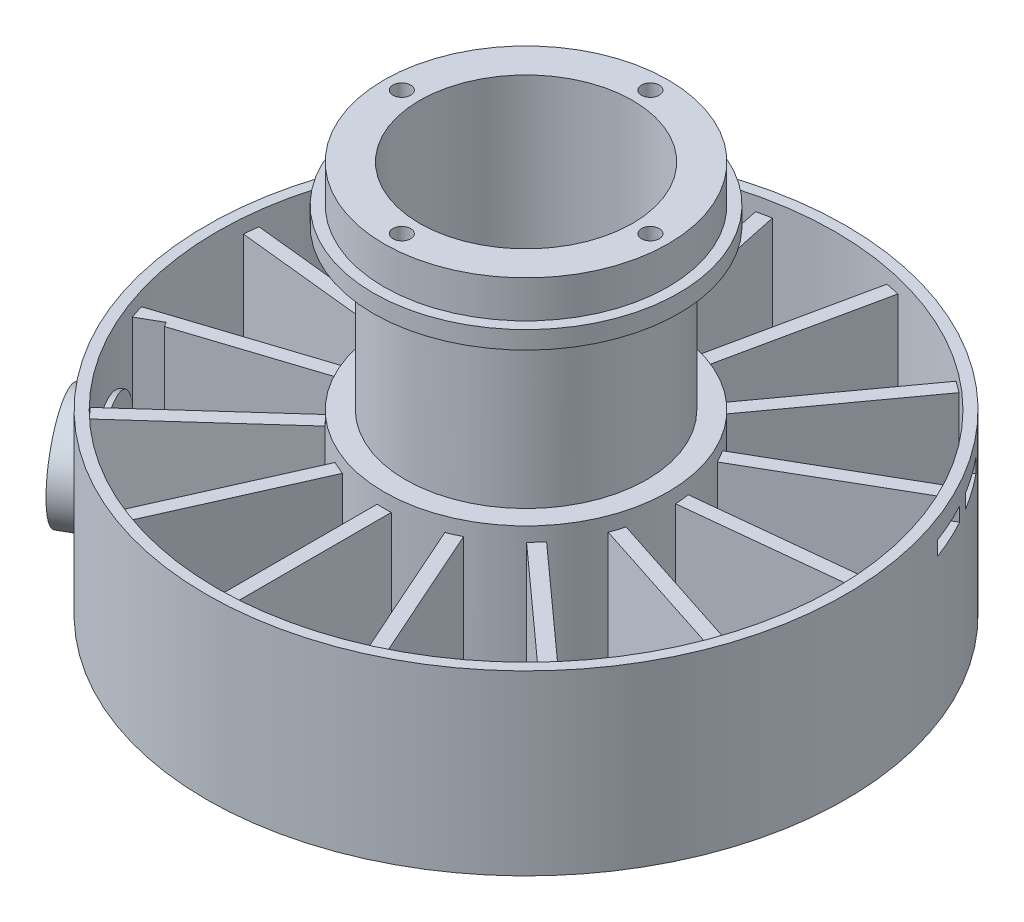
SolidWorks part; units mm, degrees
ref_plane "Front Plane" through (0, 0, 0) normal (0, 0, 1) x (1, 0, 0)
ref_plane "Top Plane" through (0, 0, 0) normal (0, 1, 0) x (1, 0, 0)
ref_plane "Right Plane" through (0, 0, 0) normal (1, 0, 0) x (0, 0, -1)
sketch "Sketch1" plane through (0, 0, 0) normal (0, 1, 0) x (1, 0, 0)
  circle A0 centre (0, 0) radius 90
  dimension "D1" = 180
extrude "Boss-Extrude1" add sketch "Sketch1" along normal blind 50
sketch "Sketch2" plane through (0, 0, 0) normal (0, -1, 0) x (1, 0, 0)
  line L0 (0, 90) -> (0, 0) construction
  line L1 (-2, 89.9778) -> (-2, 0)
  line L2 (-2, 0) -> (2, 0)
  line L3 (2, 0) -> (2, 89.9778)
  line L4 (34.7702, 83.0123) -> (-1.8271, 0.8135)
  line L5 (-1.8271, 0.8135) -> (1.8271, -0.8135)
  line L6 (1.8271, -0.8135) -> (38.4243, 81.3853)
  line L7 (36.6063, 82.2191) -> (0, 0) construction
  line L8 (65.5283, 61.6932) -> (-1.3383, 1.4863)
  line L9 (-1.3383, 1.4863) -> (1.3383, -1.4863)
  line L10 (1.3383, -1.4863) -> (68.2048, 58.7206)
  line L11 (66.883, 60.2218) -> (0, 0) construction
  line L12 (84.9559, 29.7068) -> (-0.618, 1.9021)
  line L13 (-0.618, 1.9021) -> (0.618, -1.9021)
  line L14 (0.618, -1.9021) -> (86.192, 25.9025)
  line L15 (85.5951, 27.8115) -> (0, 0) construction
  line L16 (89.6939, -7.4162) -> (0.2091, 1.989)
  line L17 (0.2091, 1.989) -> (-0.2091, -1.989)
  line L18 (-0.2091, -1.989) -> (89.2758, -11.3943)
  line L19 (89.507, -9.4076) -> (0, 0) construction
  line L20 (78.923, -43.2568) -> (1, 1.7321)
  line L21 (1, 1.7321) -> (-1, -1.7321)
  line L22 (-1, -1.7321) -> (76.923, -46.7209)
  line L23 (77.9423, -45) -> (0, 0) construction
  line L24 (54.5056, -71.618) -> (1.618, 1.1756)
  line L25 (1.618, 1.1756) -> (-1.618, -1.1756)
  line L26 (-1.618, -1.1756) -> (51.2696, -73.9691)
  line L27 (52.9007, -72.8115) -> (0, 0) construction
  line L28 (20.6637, -87.5957) -> (1.9563, 0.4158)
  line L29 (1.9563, 0.4158) -> (-1.9563, -0.4158)
  line L30 (-1.9563, -0.4158) -> (16.7511, -88.4274)
  line L31 (18.7121, -88.0333) -> (0, 0) construction
  line L32 (-16.7511, -88.4274) -> (1.9563, -0.4158)
  line L33 (1.9563, -0.4158) -> (-1.9563, 0.4158)
  line L34 (-1.9563, 0.4158) -> (-20.6637, -87.5957)
  line L35 (-18.7121, -88.0333) -> (0, 0) construction
  line L36 (-51.2696, -73.9691) -> (1.618, -1.1756)
  line L37 (1.618, -1.1756) -> (-1.618, 1.1756)
  line L38 (-1.618, 1.1756) -> (-54.5056, -71.618)
  line L39 (-52.9007, -72.8115) -> (0, 0) construction
  line L40 (-76.923, -46.7209) -> (1, -1.7321)
  line L41 (1, -1.7321) -> (-1, 1.7321)
  line L42 (-1, 1.7321) -> (-78.923, -43.2568)
  line L43 (-77.9423, -45) -> (0, 0) construction
  line L44 (-89.2758, -11.3943) -> (0.2091, -1.989)
  line L45 (0.2091, -1.989) -> (-0.2091, 1.989)
  line L46 (-0.2091, 1.989) -> (-89.6939, -7.4162)
  line L47 (-89.507, -9.4076) -> (0, 0) construction
  line L48 (-86.192, 25.9025) -> (-0.618, -1.9021)
  line L49 (-0.618, -1.9021) -> (0.618, 1.9021)
  line L50 (0.618, 1.9021) -> (-84.9559, 29.7068)
  line L51 (-85.5951, 27.8115) -> (0, 0) construction
  line L52 (-68.2048, 58.7206) -> (-1.3383, -1.4863)
  line L53 (-1.3383, -1.4863) -> (1.3383, 1.4863)
  line L54 (1.3383, 1.4863) -> (-65.5283, 61.6932)
  line L55 (-66.883, 60.2218) -> (0, 0) construction
  line L56 (-38.4243, 81.3853) -> (-1.8271, -0.8135)
  line L57 (-1.8271, -0.8135) -> (1.8271, 0.8135)
  line L58 (1.8271, 0.8135) -> (-34.7702, 83.0123)
  line L59 (-36.6063, 82.2191) -> (0, 0) construction
  circle A0 centre (0, 0) radius 90
  point P155 (0, 0)
  circle M2 centre (0, 0) radius 90
  dimension "D1" = 180
  dimension "D2" = 4
  dimension "D3" = 15
extrude "Cut-Extrude1" cut sketch "Sketch2" against normal blind 50 contours L48 L46 M2 | L52 L50 M2 | L56 L54 M2 | L58 L1 M2 | L4 L3 M2 | L8 L6 M2 | L12 L10 M2 | L16 L14 M2 | L20 L18 M2 | L24 L22 M2 | L28 L26 M2 | L32 L30 M2 | L36 L34 M2 | L40 L38 M2 | L44 L42 M2 region at (-13.0686, 0, 61.4828) region at (13.0686, 0, 61.4828) region at (-36.9461, 0, 50.8519) region at (36.9461, 0, 50.8519) region at (-54.4352, 0, 31.4282) region at (54.4352, 0, 31.4282) region at (-62.5121, 0, 6.5703) region at (62.5121, 0, 6.5703) region at (-59.78, 0, -19.4237) region at (59.78, 0, -19.4237) region at (-46.7114, 0, -42.0591) region at (46.7114, 0, -42.0591) region at (-25.566, 0, -57.4222) region at (25.566, 0, -57.4222) region at (0, 0, -62.8564)
sketch "Sketch4" plane through (0, 50, 0) normal (0, 1, 0) x (1, 0, 0)
  circle A0 centre (0, 0) radius 40
  dimension "D1" = 80
extrude "Cut-Extrude2" cut sketch "Sketch4" against normal through all
sketch "Sketch5" plane through (0, 50, 0) normal (0, 1, 0) x (1, 0, 0)
  circle A0 centre (0, 0) radius 40
  circle A1 centre (0, 0) radius 34
extrude "Boss-Extrude2" add sketch "Sketch5" against normal blind 50
sketch "Sketch9" plane through (0, 50, 0) normal (0, 1, 0) x (1, 0, 0)
  circle A0 centre (0, 0) radius 30
  circle A2 centre (0, 0) radius 34
  circle A4 centre (0, 0) radius 34 construction
  dimension "D1" = 60
extrude "Boss-Extrude3" add sketch "Sketch9" against normal blind 15 and the other way blind 50
sketch "Sketch10" plane through (0, 100, 0) normal (0, 1, 0) x (1, 0, 0)
  circle A0 centre (0, 0) radius 40
  circle A1 centre (0, 0) radius 30 construction
  circle A2 centre (0, 0) radius 30
extrude "Boss-Extrude4" add sketch "Sketch10" along normal blind 10.5
sketch "Sketch11" plane through (0, 0, 0) normal (0, -1, 0) x (1, 0, 0)
  circle A0 centre (0, 0) radius 90
  circle A1 centre (0, 0) radius 87
  dimension "D1" = 174
extrude "Boss-Extrude5" add sketch "Sketch11" against normal up to surface (50 mm away) up to face at (13.5105, 50, -63.5619)
sketch "Sketch12" plane through (0, 50, 0) normal (0, 1, 0) x (1, 0, 0)
  circle A0 centre (0, 0) radius 40
  circle A1 centre (0, 0) radius 87
extrude "Cut-Extrude3" cut sketch "Sketch12" against normal blind 4
sketch "Sketch13" plane through (0, 0, 0) normal (0, -1, 0) x (1, 0, 0)
  circle A0 centre (0, 0) radius 87
extrude "Cut-Extrude4" cut sketch "Sketch13" against normal blind 4
ref_plane "Plane1" through (0, 110.5, 0) normal (0, 1, 0) x (1, 0, 0)
sketch "Sketch15" plane through (0, 100, 0) normal (0, -1, 0) x (1, 0, 0)
  circle A0 centre (0, 0) radius 43
  circle A1 centre (0, 0) radius 34 construction
  circle A2 centre (0, 0) radius 34
  dimension "D1" = 86
extrude "Boss-Extrude6" add sketch "Sketch15" along normal blind 5
sketch "Sketch14" plane through (0, 110.5, 0) normal (0, 1, 0) x (1, 0, 0)
  circle A0 centre (0, 0) radius 35
  circle A1 centre (-35, 0) radius 2.5
  circle A2 centre (0, 35) radius 2.5
  circle A3 centre (35, 0) radius 2.5
  circle A4 centre (0, -35) radius 2.5
  arc A5 (76.3243, 41.7565) -> (74.3243, 45.2206) centre (0, 0) ccw construction
  arc A6 (76.3243, 41.7565) -> (74.3243, 45.2206) centre (0, 0) ccw
  point P3 (-35, 0)
  point P4 (0, 35)
  point P5 (35, 0)
  point P6 (0, -35)
  point P10 (-35, 0)
  dimension "D1" = 70
extrude "Cut-Extrude5" cut sketch "Sketch14" against normal blind 15 contours A0 A4 | A0 A4 | A0 A2 | A0 A2 | A0 A1 | A0 A3 | A0 A3 | A1 region at (33.923, 110.5, 0) region at (36.0448, 110.5, 0) region at (0, 110.5, -33.923) region at (0, 110.5, -36.0448) region at (0, 110.5, 36.0448) region at (0, 110.5, 33.923) region at (-33.923, 110.5, 0)
ref_plane "Plane2" through (75.3243, 0, -43.4885) normal (-0.866, 0, 0.5) x (0.5, 0, 0.866)
sketch "Sketch16" plane through (75.3243, 0, -43.4885) normal (-0.866, 0, 0.5) x (0.5, 0, 0.866)
  line L0 (2, 46) -> (-2, 46) construction
  line L5 (-2.25, 44.625) -> (-14.75, 44.625)
  line L6 (-2.25, 44.625) -> (-2.25, 40.625)
  line L7 (-2.25, 40.625) -> (-14.75, 40.625)
  line L8 (-14.75, 44.625) -> (-14.75, 40.625)
  line L9 (2, 46) -> (-2, 46) construction
  line L10 (0, 46) -> (0, 39.2296) construction
  line L11 (14.75, 44.625) -> (14.75, 40.625)
  line L12 (2.25, 40.625) -> (14.75, 40.625)
  line L13 (2.25, 44.625) -> (2.25, 40.625)
  line L14 (2.25, 44.625) -> (14.75, 44.625)
  point P10 (0, 46)
  dimension "D1" = 2.25
  dimension "D2" = 12.5
  dimension "D3" = 4
  dimension "D4" = 2.75
extrude "Cut-Extrude6" cut sketch "Sketch16" against normal blind 10 and the other way blind 10
sketch "Sketch17" plane through (0, 46, 0) normal (0, 1, 0) x (1, 0, 0)
  arc A0 (76.3243, 41.7565) -> (74.3243, 45.2206) centre (0, 0) ccw construction
  point P0 (75.3442, 43.5)
ref_plane "Plane3" through (-74.0384, 0, 42.7461) normal (-0.866, 0, 0.5) x (0.5, 0, 0.866)
sketch "Sketch19" plane through (-74.0384, 0, 42.7461) normal (-0.866, 0, 0.5) x (0.5, 0, 0.866)
  line L0 (90, 50) -> (-90, 50) construction
  line L1 (0, 0) -> (0, 45.8895) construction
  circle A0 centre (-2, 20) radius 11
  dimension "D2" = 22
  dimension "D1" = 30
  dimension "D3" = 2
extrude "Cut-Extrude7" cut sketch "Sketch19" against normal blind 10 and the other way blind 10
sketch "Sketch20" plane through (-74.0384, 0, 42.7461) normal (-0.866, 0, 0.5) x (0.5, 0, 0.866)
  circle A0 centre (-2, 20) radius 11 construction
  circle A1 centre (-2, 20) radius 11
  circle A2 centre (-2, 20) radius 14.9592
extrude "Boss-Extrude7" add sketch "Sketch20" along normal blind 10
sketch "Sketch21" plane through (0, 46, 0) normal (0, 1, 0) x (1, 0, 0)
  line L0 (-82.102, -28.7795) -> (-76.0398, -25.2795)
  line L1 (-76.0398, -25.2795) -> (-75.2959, -26.568)
  line L2 (-37.3766, -14.2473) -> (-82.102, -28.7795) construction
  line L3 (-67.5588, -53.9691) -> (-82.102, -28.7795) construction
  line L4 (-67.5588, -53.9691) -> (-82.102, -28.7795) construction
  line L5 (-75.2959, -26.568) -> (-82.102, -28.7795)
  dimension "D1" = 7
extrude "Cut-Extrude8" cut sketch "Sketch21" against normal through all
